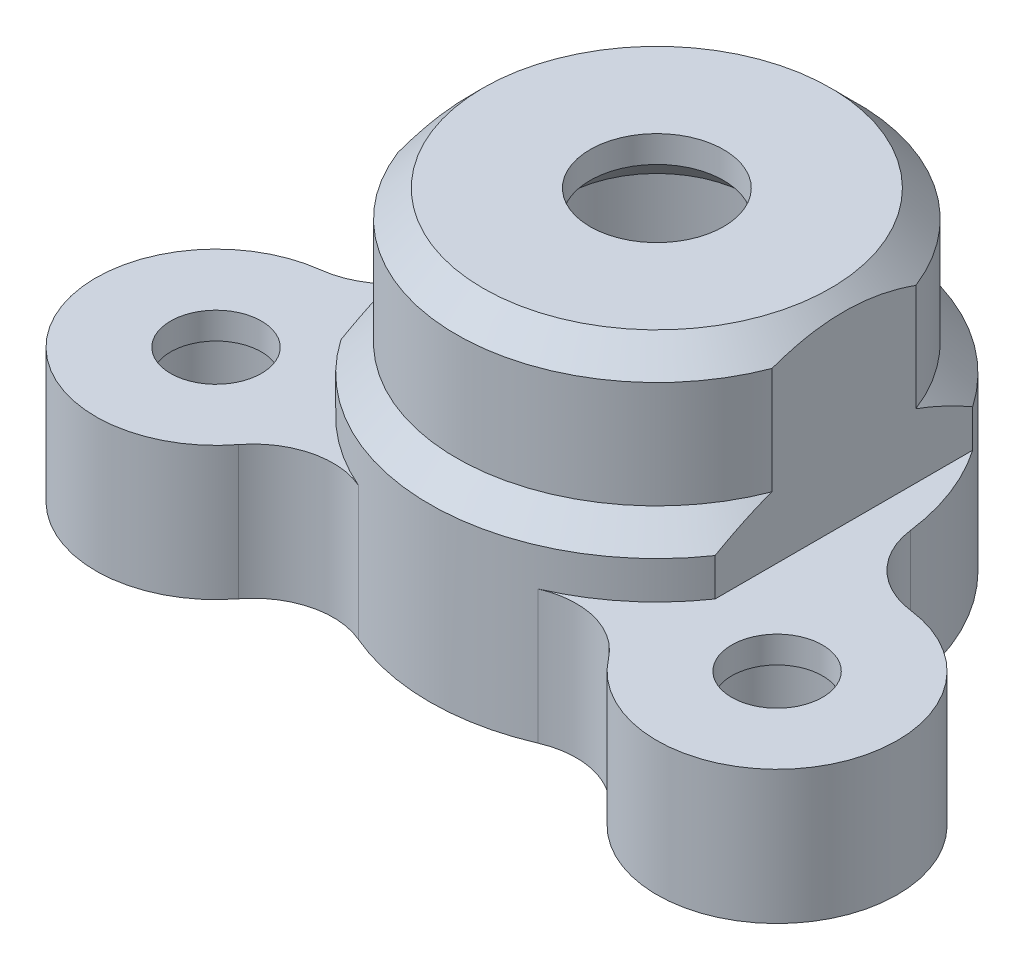
SolidWorks part; units mm, degrees
ref_plane "Plan de face" through (0, 0, 0) normal (0, 0, 1) x (1, 0, 0)
ref_plane "Plan de dessus" through (0, 0, 0) normal (0, 1, 0) x (1, 0, 0)
ref_plane "Plan de droite" through (0, 0, 0) normal (1, 0, 0) x (0, 0, -1)
sketch "Esquisse1" plane through (0, 0, 0) normal (0, 1, 0) x (1, 0, 0)
  line L0 (0, 8.5) -> (0, -8.5) construction
  line L1 (0, 0) -> (-7.3612, 4.25) construction
  line L2 (0, 0) -> (7.3612, 4.25) construction
  line L3 (-10.5, -1.5) -> (-6.3246, -1.5)
  line L4 (10.5, -1.5) -> (6.3246, -1.5)
  circle A0 centre (0, 0) radius 5.5 construction
  circle A2 centre (-10.5, -6) radius 1.7 construction
  arc A3 (-6, -6.0207) -> (6, -6.0207) centre (0, 0) ccw
  circle A4 centre (-10.5, -6) radius 2.5
  arc A5 (-10.5, -1.5) -> (-6, -6.0207) centre (-10.5, -6) ccw
  circle A6 centre (0, 0) radius 6.5
  circle A8 centre (10.5, -6) radius 1.7 construction
  circle A10 centre (10.5, -6) radius 2.5
  arc A11 (10.5, -1.5) -> (6, -6.0207) centre (10.5, -6) cw
  arc A12 (8.3666, -1.5) -> (-8.3666, -1.5) centre (0, 0) ccw construction
  dimension "D1" = 11
  dimension "D4" = 3.4
  dimension "D5" = 2
  dimension "D6" = 3
  dimension "D7" = 5
  dimension "D9" = 1
  dimension "D2" = 10.5
  dimension "D3" = 6
  dimension "D10" = 60
  dimension "D11" = 60
sketch "Esquisse2" plane through (0, 0, 0) normal (0, 0, 1) x (1, 0, 0)
  line L0 (0, 9) -> (0, 0) construction
  line L1 (-2.5, 9) -> (-2.5, 8)
  line L2 (-2.5, 8) -> (-3.5, 7)
  line L3 (-3.5, 7) -> (-5.5, 7)
  line L4 (-5.5, 7) -> (-5.5, 3)
  line L5 (-5.5, 3) -> (-6.5, 2)
  line L7 (-8.5, 0) -> (-8.5, 3)
  line L8 (-8.5, 9) -> (-7.5, 9) construction
  line L9 (-6.5, 2) -> (-6.5, 0)
  line L10 (-8.5, 3) -> (-7.5, 4)
  line L11 (-6.5, 0) -> (-8.5, 0)
  line L12 (-7.5, 4) -> (-7.5, 8)
  line L13 (-8.5, 3) -> (-8.5, 9) construction
  line L14 (-6.5, 9) -> (-2.5, 9)
  line L15 (-7.5, 8) -> (-6.5, 9)
  dimension "D1" = 2.5
  dimension "D2" = 5.5
  dimension "D3" = 2
  dimension "D4" = 1
  dimension "D5" = 1
  dimension "D6" = 4
  dimension "D7" = 1
  dimension "D8" = 8.5
  dimension "D9" = 2
  dimension "D10" = 1
  dimension "D11" = 1
revolve "Révolution1" add sketch "Esquisse2" angle 360 about L0
extrude "Boss.-Extru.1" add sketch "Esquisse1" against normal blind 5 from offset 1.5917 contours A11 A6 A5 A3 A4 A10 | A4 | A10 region at (-8.4123, 0, 1.8132) region at (-10.5, 0, 6) region at (10.5, 0, 6)
extrude "Enlèv. mat.-Extru.3" cut sketch "Esquisse1<7>" along normal blind 4 from surface contours A4 | A10 region at (-10.5, 0, 6) region at (10.5, 0, 6) starting at face at (0, -3.4082, 6.0582)
sketch "Esquisse1<7>" plane through (0, 0, 0) normal (0, 1, 0) x (1, 0, 0) same geometry as "Esquisse1"
sketch "Esquisse9" plane through (0, -3.4082, 0) normal (0, -1, 0) x (-1, 0, 0)
  point P0 (-10.5, -6)
  point P3 (10.5, -6)
hole_wizard "M3 Clearance Hole2" positions "Esquisse9" profile "Esquisse8" hole size "M3" standard "ANSI Metric" end condition up to next
sketch "Esquisse8" plane through (10.5, -3.4082, 6) normal (1, 0, 0) x (0, 0, -1)
  line L0 (0, 0) -> (0, 5)
  line L1 (0, 5) -> (1.7, 5)
  line L2 (1.7, 5) -> (1.7, 0)
  line L5 (1.7, 0) -> (0, 0)
  line L11 (0, -6.35) -> (0, 107.95) construction
  dimension "Thru Hole Dia." = 3.4
  dimension "Thru Hole Depth" = 5
sketch "Esquisse10" plane through (0, -3.4082, 0) normal (0, -1, 0) x (1, 0, 0)
  line L3 (10.5, 1.5) -> (6.3246, 1.5) construction
  line L4 (8.3666, 1.5) -> (6.3246, 1.5) construction
  line L5 (6.3246, 1.5) -> (8.3666, 1.5)
  line L6 (-6.3246, 1.5) -> (-8.3666, 1.5)
  arc A1 (-8.3666, 1.5) -> (8.3666, 1.5) centre (0, 0) ccw
  arc A2 (-6.3246, 1.5) -> (6.3246, 1.5) centre (0, 0) ccw
  line M19 (-10.5, 1.5) -> (-6.3246, 1.5)
  line M21 (6.3246, 1.5) -> (10.5, 1.5)
extrude "Boss.-Extru.3" add sketch "Esquisse10" along normal up to surface from surface contours A2 A1 M19 | A2 A1 | A2 A1 M21 region at (7.3456, -3.4082, 1.3028) up to face at (-10.5, -3.4082, 8.5) starting at face at (0, 0, -3)
sketch "Esquisse11" plane through (0, 9, 0) normal (0, 1, 0) x (1, 0, 0)
  line L0 (-7, 4.8218) -> (-7, -4.8218)
  line L1 (7, 4.8218) -> (7, -4.8218)
  circle A0 centre (0, 0) radius 8.5 construction
  arc A1 (-8.3666, -1.5) -> (-6, -6.0207) centre (0, 0) ccw construction
  arc A2 (-7, -4.8218) -> (-7, 4.8218) centre (0, 0) cw
  arc A3 (7, 4.8218) -> (7, -4.8218) centre (0, 0) cw
  dimension "D1" = 14
extrude "Enlèv. mat.-Extru.5" cut sketch "Esquisse11" against normal up to surface (7.4082 mm away) contours A2 L0 | A3 L1 region at (-7.6048, 9, 0) region at (7.6048, 9, 0) up to face at (-10.5, 1.5918, 7.7)
fillet "Congé5" radius 3 4 edges at (-8.3666, -0.9082, 1.5) (8.3666, -0.9083, 1.5) (6, -0.9082, 6.0207) (-6, -0.9082, 6.0207)
chamfer "Chanfrein5" distance 0.5 angle 45 2 edges at (-10.5, -3.4082, 8.5) (10.5, -3.4082, 8.5)
